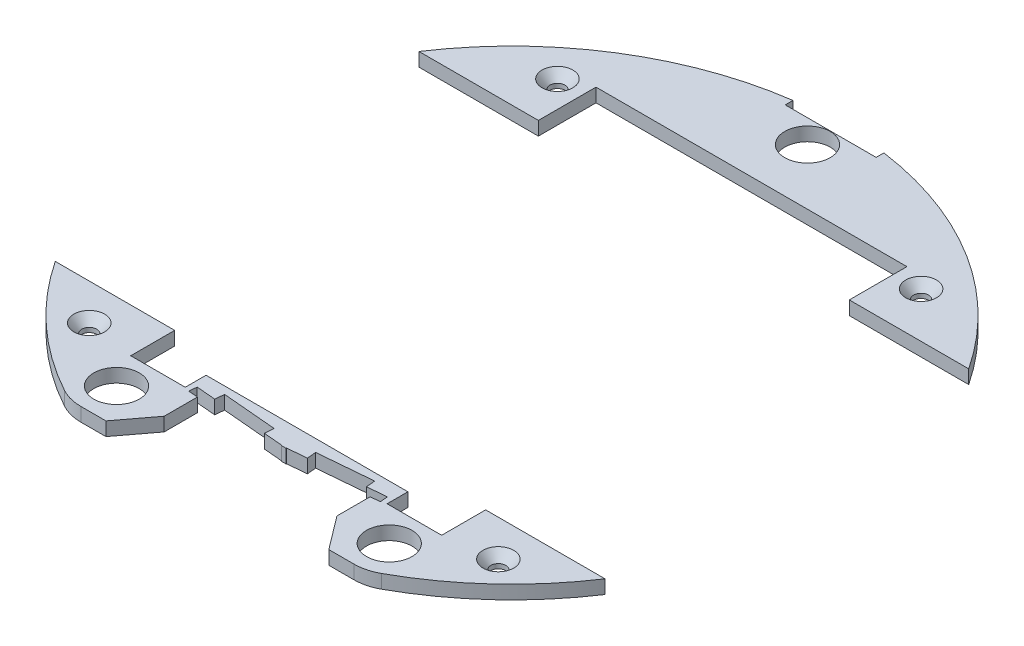
SolidWorks part; units mm, degrees
ref_plane "Front Plane" through (0, 0, 0) normal (0, 0, 1) x (1, 0, 0)
ref_plane "Top Plane" through (0, 0, 0) normal (0, 1, 0) x (1, 0, 0)
ref_plane "Right Plane" through (0, 0, 0) normal (1, 0, 0) x (0, 0, -1)
sketch "Sketch1" plane through (0, 0, 0) normal (0, 1, 0) x (1, 0, 0)
  line L0 (-30.03, -64.8129) -> (30.03, -64.8129)
  line L1 (0, -85) -> (0, 0) construction
  line L2 (0, -85) -> (32.4891, -64.8129) construction
  arc A0 (34.8348, -63.5829) -> (-34.8348, -63.5829) centre (0, 0) ccw
  circle A1 centre (0, -85) radius 38.25 construction
  arc A2 (30.03, -64.8129) -> (34.8348, -63.5829) centre (30.03, -54.8129) ccw
  arc A3 (-30.03, -64.8129) -> (-34.8348, -63.5829) centre (-30.03, -54.8129) cw
  dimension "D1" = 145
  dimension "D2" = 76.5
  dimension "D4" = 10
  dimension "D3" = 85
extrude "Boss-Extrude1" add sketch "Sketch1" along normal blind 3
sketch "Sketch2" plane through (0, 3, 0) normal (0, 1, 0) x (1, 0, 0)
  line L5 (22.2, -49.6757) -> (22.2, -45.1)
  line L6 (22.2, -45.1) -> (-22.2, -45.1)
  line L7 (-22.2, -45.1) -> (-22.2, -49.6757)
  line L8 (22.2, 49.6757) -> (22.2, 45.5)
  line L9 (-34.2, -49.6757) -> (-22.2, -49.6757) construction
  line L10 (-34.2, -49.6757) -> (-34.2, 49.6757) construction
  line L11 (-34.2, 49.6757) -> (-22.2, 49.6757) construction
  line L19 (34.2, 49.6757) -> (22.2, 49.6757) construction
  line L20 (34.2, -49.6757) -> (34.2, 49.6757) construction
  line L21 (34.2, -49.6757) -> (22.2, -49.6757) construction
  line L22 (22.2, 45.5) -> (-22.2, 45.5)
  line L23 (-22.2, 45.5) -> (-22.2, 49.6757)
  line L35 (-34.2, -49.6757) -> (-22.2, -49.6757)
  line L36 (-34.2, -49.6757) -> (-34.2, 49.6757)
  line L37 (-34.2, 49.6757) -> (-22.2, 49.6757)
  line L55 (34.2, 49.6757) -> (22.2, 49.6757)
  line L56 (34.2, -49.6757) -> (34.2, 49.6757)
  line L57 (34.2, -49.6757) -> (22.2, -49.6757)
  dimension "D1" = 45.1
  dimension "D2" = 45.5
extrude "Cut-Extrude1" cut sketch "Sketch2" against normal through all contours L55 L37 L36 L35 L7 L6 L5 L57 L56 region at (0, 3, -0.1256)
sketch "Sketch3" plane through (0, 3, 0) normal (0, 1, 0) x (1, 0, 0)
  line L0 (-34.2, 40) -> (-34.2, -40)
  line L1 (-72.5, -40) -> (-34.2, -40)
  line L2 (-72.5, -40) -> (-72.5, 40)
  line L3 (-72.5, 40) -> (-34.2, 40)
  line L4 (72.5, -40) -> (72.5, 40)
  line L5 (-72.5, -40) -> (72.5, 40) construction
  line L6 (-72.5, 40) -> (72.5, -40) construction
  line L7 (-34.2, -49.6757) -> (-34.2, 49.6757) construction
  line L8 (34.2, 40) -> (34.2, -40)
  line L9 (34.2, -49.6757) -> (34.2, 49.6757) construction
  line L10 (34.2, 40) -> (72.5, 40)
  line L11 (34.2, -40) -> (72.5, -40)
  arc A0 (34.8348, -63.5829) -> (-34.8348, -63.5829) centre (0, 0) ccw construction
  point P0 (0, 0)
  dimension "D1" = 80
extrude "Cut-Extrude2" cut sketch "Sketch3" against normal through all
sketch "Sketch4" plane through (0, 3, 0) normal (0, 1, 0) x (1, 0, 0)
  line L0 (-21.0702, -50.0262) -> (-0.6482, -51.8129)
  line L1 (21.0702, -50.0262) -> (20.922, -48.3326)
  line L2 (0.6482, -51.8129) -> (0.5, -50.1193)
  line L3 (20.922, -48.3326) -> (0.5, -50.1193)
  line L4 (0, 0) -> (0, -64.8129) construction
  line L5 (-30.03, -64.8129) -> (30.03, -64.8129) construction
  line L6 (-20.922, -48.3326) -> (-0.5, -50.1193)
  line L7 (-0.6482, -51.8129) -> (-0.5, -50.1193)
  line L8 (-21.0702, -50.0262) -> (-20.922, -48.3326)
  line L14 (21.0702, -50.0262) -> (0.6482, -51.8129)
  dimension "D1" = 1.7
  dimension "D2" = 20.5
  dimension "D3" = 5
  dimension "D4" = 13
  dimension "D5" = 0.5
extrude "Cut-Extrude3" cut sketch "Sketch4" against normal through all
sketch "Sketch5" plane through (0, 3, 0) normal (0, 1, 0) x (1, 0, 0)
  line L0 (-19, -64.8129) -> (-19, -50.2073)
  line L4 (0.6482, -51.8129) -> (21.0702, -50.0262) construction
  line L5 (16.6882, -48.7031) -> (4.7338, -49.7489)
  line L6 (16.6882, -48.7031) -> (16.5139, -46.7107)
  line L7 (4.7338, -49.7489) -> (4.5595, -47.7565)
  line L8 (16.5139, -46.7107) -> (4.5595, -47.7565)
  line L9 (20.922, -48.3326) -> (0.5, -50.1193) construction
  line L10 (0, 0) -> (0, -50.2073) construction
  line L11 (19, -64.8129) -> (19, -50.2073)
  line L13 (-16.5139, -46.7107) -> (-4.5595, -47.7565)
  line L14 (-4.7338, -49.7489) -> (-4.5595, -47.7565)
  line L15 (-16.6882, -48.7031) -> (-16.5139, -46.7107)
  line L16 (-16.6882, -48.7031) -> (-4.7338, -49.7489)
  line L22 (-30.03, -64.8129) -> (30.03, -64.8129) construction
  line L23 (19, -50.2073) -> (-19, -50.2073)
  line L25 (-19, -64.8129) -> (19, -64.8129)
  point P14 (10.711, -49.226)
  point P15 (10.711, -49.226)
  dimension "D1" = 12
  dimension "D2" = 38
  dimension "D4" = 2
extrude "Cut-Extrude4" cut sketch "Sketch5" against normal through all
sketch "Sketch6" plane through (0, 3, 0) normal (0, 1, 0) x (1, 0, 0)
  line L1 (34.2, 49.6757) -> (-34.2, 49.6757)
  line L2 (34.2, 49.6757) -> (34.2, 52.6757)
  line L3 (34.2, 52.6757) -> (-34.2, 52.6757)
  line L4 (-34.2, 49.6757) -> (-34.2, 52.6757)
  dimension "D1" = 3
extrude "Cut-Extrude5" cut sketch "Sketch6" against normal through all body kept at (60.4669, 0, -40)
sketch "Sketch7" plane through (0, 3, 0) normal (0, 1, 0) x (1, 0, 0)
  line L0 (0, 0) -> (0, -31.2827) construction
  circle A0 centre (-30, -57) radius 5
  circle A4 centre (30, -57) radius 5
  dimension "D1" = 10
  dimension "D2" = 30
  dimension "D3" = 57
extrude "Cut-Extrude6" cut sketch "Sketch7" against normal through all
sketch "Sketch11" plane through (0, 3, 0) normal (0, 1, 0) x (1, 0, 0)
  line L0 (0, 0) -> (0, 65) construction
  circle A0 centre (0, 65) radius 5
  dimension "D2" = 10
  dimension "D1" = 65
extrude "Cut-Extrude10" cut sketch "Sketch11" against normal through all
sketch "Sketch13" plane through (0, 3, 0) normal (0, 1, 0) x (1, 0, 0)
  line L0 (19, -57.5101) -> (24.515, -64.8129)
  line L1 (19, -64.8129) -> (19, -50.2073) construction
  line L2 (19, -64.8129) -> (30.03, -64.8129) construction
  line L3 (24.515, -64.8129) -> (19, -64.8129)
  line L4 (19, -64.8129) -> (19, -57.5101)
  line L5 (0, 0) -> (0, -25.0729) construction
  line L6 (-19, -64.8129) -> (-19, -57.5101)
  line L7 (-24.515, -64.8129) -> (-19, -64.8129)
  line L8 (-19, -57.5101) -> (-24.515, -64.8129)
extrude "Cut-Extrude11" cut sketch "Sketch13" against normal through all
sketch "Sketch14" plane through (0, 3, 0) normal (0, 1, 0) x (1, 0, 0)
  line L1 (0, 0) -> (0, -20.685) construction
  circle A0 centre (45, -48) radius 1.65
  circle A1 centre (-45, -48) radius 1.65
  circle A2 centre (40, 50) radius 1.65
  circle A3 centre (-40, 50) radius 1.65
  dimension "D3" = 3.3
  dimension "D1" = 45
  dimension "D2" = 48
  dimension "D4" = 40
  dimension "D5" = 50
extrude "Cut-Extrude12" cut sketch "Sketch14" against normal through all
sketch "Sketch15" plane through (0, 3, 0) normal (0, 1, 0) x (1, 0, 0)
  line L1 (10, 71.807) -> (-10, 71.807)
  line L2 (10, 71.807) -> (10, 70.107)
  line L3 (10, 70.107) -> (-10, 70.107)
  line L4 (-10, 71.807) -> (-10, 70.107)
  arc A0 (60.4669, 40) -> (-60.4669, 40) centre (0, 0) ccw construction
  dimension "D1" = 20
  dimension "D2" = 1.7
extrude "Cut-Extrude13" cut sketch "Sketch15" against normal blind 10
chamfer "Chamfer1" distance 2 angle 41 2 edges at (-45, 3, 46.35) (45, 3, 49.65) first distance on face at (-45, 0, 46.35) first distance on face at (45, 0, 49.65)
chamfer "Chamfer2" distance 2 angle 41 2 edges at (-40, 3, -51.65) (40, 3, -48.35) first distance on face at (-40, 0, -51.65) first distance on face at (40, 0, -48.35)
equation "\"smallPulleyTeeth\"= 30"
equation "\"largePulleyTeeth\"= 30"
equation "\"eighthThick\"= 3.0mm"
equation "\"sixteenthThick\"= 1.7mm"
equation "\"quarterThick\"=6.0mm"
equation "\"OD\"= 145mm"
equation "\"puckAngle\"= 60.5deg"
equation "\"puckDiam\"= 76.5mm"
equation "\"axlePress\"= 5.9mm"
equation "\"press\"= 0.2mm"
equation "\"wheelClear\"= 0.3mm"
equation "\"10-32clear\"= 4.8mm"
equation "\"6-32clear\"= 3.3mm"
equation "\"8-32clear\"= 4.0mm"
equation "\"4-40clear\"= 3.0mm"
equation "\"wheelHeight\"= 22mm"
equation "\"wheelWell\"= 65mm"
equation "\"D1@Sketch1\"=\"OD\""
equation "\"D1@Boss-Extrude1\"=\"eighthThick\""
equation "\"D2@Sketch1\"=\"puckDiam\""
equation "\"puckDist\"= 85mm"
equation "\"scoopFillet\"= 5mm"
equation "\"10-32tap\"= 4.45mm"
equation "\"ledSmall\"= 3.1mm"
equation "\"ledLarge\"= 4.2mm"
equation "\"ledLength\"= 4.2mm"
equation "\"D3@Sketch1\"=\"puckDist\""
equation "\"D1@Sketch6\"=\"eighthThick\""
equation "\"D2@Sketch15\"=\"sixteenthThick\""
